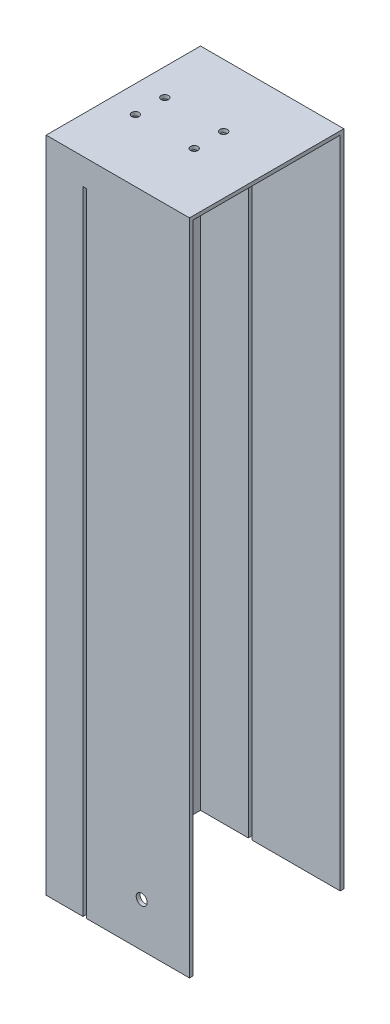
SolidWorks part; units mm, degrees
ref_plane "Alzado" through (0, 0, 0) normal (0, 0, 1) x (1, 0, 0)
ref_plane "Planta" through (0, 0, 0) normal (0, 1, 0) x (1, 0, 0)
ref_plane "Vista lateral" through (0, 0, 0) normal (1, 0, 0) x (0, 0, -1)
sketch "Sketch1" plane through (0, 0, 0) normal (1, 0, 0) x (0, 0, -1)
  line L1 (-13.831, 10.0882) -> (28.169, 10.0882)
  line L2 (-13.831, 10.0882) -> (-13.831, -159.9118)
  line L3 (-13.831, -159.9118) -> (28.169, -159.9118)
  line L4 (28.169, 10.0882) -> (28.169, -159.9118)
  dimension "D1" = 42
  dimension "D2" = 170
extrude "Boss-Extrude1" add sketch "Sketch1" along normal blind 1
sketch "Sketch2" plane through (1, 0, 0) normal (1, 0, 0) x (0, 0, -1)
  line L0 (28.169, 10.0882) -> (-13.831, 10.0882) construction
  line L1 (28.169, -159.9118) -> (27.169, -159.9118)
  line L2 (28.169, -159.9118) -> (28.169, 10.0882)
  line L3 (28.169, 10.0882) -> (27.169, 10.0882)
  line L4 (27.169, -159.9118) -> (27.169, 10.0882)
  line L6 (-13.831, -159.9118) -> (28.169, -159.9118) construction
  line L7 (-13.831, 10.0882) -> (-12.831, 10.0882)
  line L8 (-13.831, 10.0882) -> (-13.831, -159.9118)
  line L9 (-13.831, -159.9118) -> (-12.831, -159.9118)
  line L10 (-12.831, 10.0882) -> (-12.831, -159.9118)
  dimension "D1" = 1
  dimension "D2" = 1
extrude "Boss-Extrude2" add sketch "Sketch2" along normal blind 50
sketch "Sketch4" plane through (0, 10.0882, 0) normal (0, 1, 0) x (1, 0, 0)
  line L0 (51, 28.169) -> (51, 27.169)
  line L1 (51, 27.169) -> (1, 27.169)
  line L2 (1, 27.169) -> (1, -12.831)
  line L3 (1, -12.831) -> (51, -12.831)
  line L4 (51, -12.831) -> (51, -13.831)
  line L5 (51, -13.831) -> (0, -13.831)
  line L6 (0, -13.831) -> (0, 28.169)
  line L7 (0, 28.169) -> (51, 28.169)
extrude "Boss-Extrude3" add sketch "Sketch4" along normal blind 30
sketch "Sketch5" plane through (0, -159.9118, 0) normal (0, -1, 0) x (1, 0, 0)
  line L0 (1, 12.831) -> (10, 12.831) construction
  line L1 (51, 12.831) -> (1, 12.831) construction
  line L2 (51, 13.831) -> (0, 13.831) construction
  line L3 (10, 12.831) -> (11, 12.831)
  line L4 (10, 12.831) -> (10, 13.831)
  line L5 (10, 13.831) -> (11, 13.831)
  line L6 (11, 12.831) -> (11, 13.831)
  dimension "D1" = 9
  dimension "D2" = 1
extrude "Cut-Extrude1" cut sketch "Sketch5" against normal blind 170
sketch "Sketch6" plane through (0, -159.9118, 0) normal (0, -1, 0) x (1, 0, 0)
  line L0 (10, 12.831) -> (10, -27.169) construction
  line L1 (51, -27.169) -> (1, -27.169) construction
  line L2 (10, -27.169) -> (14, -27.169) construction
  line L3 (51, -28.169) -> (0, -28.169) construction
  line L4 (14, -27.169) -> (15, -27.169)
  line L5 (14, -27.169) -> (14, -28.169)
  line L6 (14, -28.169) -> (15, -28.169)
  line L7 (15, -27.169) -> (15, -28.169)
  dimension "D1" = 4
  dimension "D2" = 1
extrude "Cut-Extrude2" cut sketch "Sketch6" against normal blind 170
sketch "Sketch9" plane through (0, 0, 13.831) normal (0, 0, 1) x (1, 0, 0)
  line L0 (11, -159.9118) -> (26, -159.9118) construction
  line L1 (51, -159.9118) -> (11, -159.9118) construction
  line L2 (26, -159.9118) -> (26, -144.9118) construction
  circle A0 centre (26, -144.9118) radius 1.5
  dimension "D1" = 15
extrude "Cut-Extrude3" cut sketch "Sketch9" against normal blind 10
sketch "Sketch10" plane through (0, 0, 13.831) normal (0, 0, 1) x (1, 0, 0)
  line L0 (26, -144.9118) -> (11, -144.9118) construction
  line L1 (11, 10.0882) -> (11, -159.9118) construction
  line L2 (26, -159.9118) -> (26, -148.9118) construction
  line L3 (51, -159.9118) -> (11, -159.9118) construction
  circle A0 centre (26, -148.9118) radius 1.5
  dimension "D1" = 11
extrude "Cut-Extrude4" cut sketch "Sketch10" against normal blind 10
sketch "Sketch11" plane through (0, 0, 13.831) normal (0, 0, 1) x (1, 0, 0)
  circle A0 centre (26, -144.9118) radius 2.0283
extrude "Boss-Extrude4" add sketch "Sketch11" against normal blind 1
sketch "Sketch13" plane through (1, 0, 0) normal (1, 0, 0) x (0, 0, -1)
  line L0 (27.169, 40.0882) -> (27.169, 10.0882) construction
  line L1 (27.169, 40.0882) -> (27.169, -159.9118) construction
  line L3 (-12.831, 40.0882) -> (27.169, 40.0882)
  line L4 (-12.831, 40.0882) -> (-12.831, 17.1882)
  line L5 (-12.831, 17.1882) -> (27.169, 17.1882)
  line L6 (27.169, 40.0882) -> (27.169, 17.1882)
  dimension "D1" = 30
  dimension "D2" = 22.9
extrude "Boss-Extrude5" add sketch "Sketch13" along normal blind 50
sketch "Sketch14" plane through (51, 0, 0) normal (1, 0, 0) x (0, 0, -1)
  line L0 (28.169, -159.9118) -> (28.169, 40.0882) construction
  line L1 (-13.831, 40.0882) -> (28.169, 40.0882)
  line L2 (-13.831, 40.0882) -> (-13.831, 18.1882)
  line L3 (-13.831, 18.1882) -> (28.169, 18.1882)
  line L4 (28.169, 40.0882) -> (28.169, 18.1882)
  dimension "D1" = 21.9
extrude "Cut-Extrude6" cut sketch "Sketch14" against normal blind 60
sketch "Sketch17" plane through (0, 17.1882, 0) normal (0, -1, 0) x (1, 0, 0)
  line L0 (1, -7.169) -> (11.5, -7.169) construction
  line L1 (1, 12.831) -> (1, -27.169) construction
  line L2 (11.5, -7.169) -> (23.29, -7.169) construction
  circle A0 centre (23.29, -11.169) radius 1
  circle A1 centre (23.29, -3.169) radius 1
  circle A2 centre (7.29, -11.169) radius 1
  circle A3 centre (7.29, -3.169) radius 1
  dimension "D3" = 4
  dimension "D5" = 16
  dimension "D1" = 10.5
  dimension "D2" = 11.79
  dimension "D4" = 4
extrude "Cut-Extrude7" cut sketch "Sketch17" against normal blind 10
sketch "Sketch18" plane through (0, -159.9118, 0) normal (0, -1, 0) x (1, 0, 0)
  line L1 (51, 12.831) -> (11, 12.831)
  line L2 (51, 12.831) -> (51, 13.831)
  line L3 (51, 13.831) -> (11, 13.831)
  line L4 (11, 12.831) -> (11, 13.831)
  line L5 (51, -28.169) -> (15, -28.169)
  line L6 (51, -28.169) -> (51, -27.169)
  line L7 (51, -27.169) -> (15, -27.169)
  line L8 (15, -28.169) -> (15, -27.169)
  line L9 (14, -28.169) -> (1, -28.169)
  line L10 (14, -28.169) -> (14, -27.169)
  line L11 (14, -27.169) -> (1, -27.169)
  line L12 (1, -28.169) -> (1, -27.169)
  line L13 (10, 13.831) -> (1, 13.831)
  line L14 (10, 13.831) -> (10, 12.831)
  line L15 (10, 12.831) -> (1, 12.831)
  line L16 (1, 13.831) -> (1, 12.831)
extrude "Boss-Extrude7" add sketch "Sketch18" along normal blind 1
sketch "Sketch19" plane through (0, -159.9118, 0) normal (0, -1, 0) x (1, 0, 0)
  line L1 (0, -28.169) -> (1, -28.169)
  line L2 (0, -28.169) -> (0, 13.831)
  line L3 (0, 13.831) -> (1, 13.831)
  line L4 (1, -28.169) -> (1, 13.831)
extrude "Boss-Extrude8" add sketch "Sketch19" along normal blind 1
sketch "Sketch20" plane through (0, 0, -28.169) normal (0, 0, -1) x (-1, 0, 0)
  line L1 (-15, 10.0882) -> (-13.9999, 10.0882)
  line L2 (-15, 10.0882) -> (-15, 11.0882)
  line L3 (-15, 11.0882) -> (-13.9999, 11.0882)
  line L4 (-13.9999, 10.0882) -> (-13.9999, 11.0882)
  dimension "D1" = 1
extrude "Cut-Extrude8" cut sketch "Sketch20" against normal blind 1
sketch "Sketch21" plane through (0, 0, 13.831) normal (0, 0, 1) x (1, 0, 0)
  line L1 (10, 10.0882) -> (11, 10.0882)
  line L2 (10, 10.0882) -> (10, 11.0882)
  line L3 (10, 11.0882) -> (11, 11.0882)
  line L4 (11, 10.0882) -> (11, 11.0882)
  dimension "D1" = 1
extrude "Cut-Extrude9" cut sketch "Sketch21" against normal blind 1
sketch "Sketch22" plane through (0, 0, 13.831) normal (0, 0, 1) x (1, 0, 0)
  line L0 (51, -160.9118) -> (11, -160.9118) construction
  line L1 (38, -160.9118) -> (39, -160.9118)
  line L2 (38, -160.9118) -> (38, -129.9118)
  line L3 (38, -129.9118) -> (39, -129.9118)
  line L4 (39, -160.9118) -> (39, -129.9118)
  dimension "D1" = 1
  dimension "D2" = 31
extrude "Boss-Extrude9" add sketch "Sketch22" against normal through all
sketch "Sketch26" plane through (0, -160.9118, 0) normal (0, -1, 0) x (-1, 0, 0)
  line L0 (-15, 28.169) -> (-51, 28.169) construction
  line L1 (-27.8775, 28.169) -> (-16.3775, 28.169)
  line L2 (-27.8775, 28.169) -> (-27.8775, -13.831)
  line L3 (-27.8775, -13.831) -> (-16.3775, -13.831)
  line L4 (-16.3775, 28.169) -> (-16.3775, -13.831)
  line L5 (-51, -13.831) -> (-11, -13.831) construction
  dimension "D1" = 11.5
extrude "Boss-Extrude13" add sketch "Sketch26" along normal blind 1
sketch "Sketch29" plane through (0, 0, 13.831) normal (0, 0, 1) x (1, 0, 0)
  circle A0 centre (26, -148.9118) radius 1.5
sketch "Sketch35" plane through (39, 0, 0) normal (1, 0, 0) x (0, 0, -1)
  line L1 (27.169, -129.9118) -> (-12.831, -129.9118)
  line L2 (27.169, -129.9118) -> (27.169, -160.9118)
  line L3 (27.169, -160.9118) -> (-12.831, -160.9118)
  line L4 (-12.831, -129.9118) -> (-12.831, -160.9118)
extrude "Cut-Extrude17" cut sketch "Sketch35" against normal blind 27
sketch "Sketch36" plane through (27.8775, 0, 0) normal (1, 0, 0) x (0, 0, -1)
  line L1 (-13.831, -160.9118) -> (28.169, -160.9118)
  line L2 (-13.831, -160.9118) -> (-13.831, -161.9118)
  line L3 (-13.831, -161.9118) -> (28.169, -161.9118)
  line L4 (28.169, -160.9118) -> (28.169, -161.9118)
extrude "Cut-Extrude18" cut sketch "Sketch36" against normal blind 24
sketch "Sketch37" plane through (0, 0, 13.831) normal (0, 0, 1) x (1, 0, 0)
  line L1 (51, -160.9118) -> (39, -160.9118)
  line L2 (51, -160.9118) -> (51, 51.8324)
  line L3 (51, 51.8324) -> (39, 51.8324)
  line L4 (39, -160.9118) -> (39, 51.8324)
  dimension "D1" = 12
extrude "Cut-Extrude19" cut sketch "Sketch37" against normal blind 50
